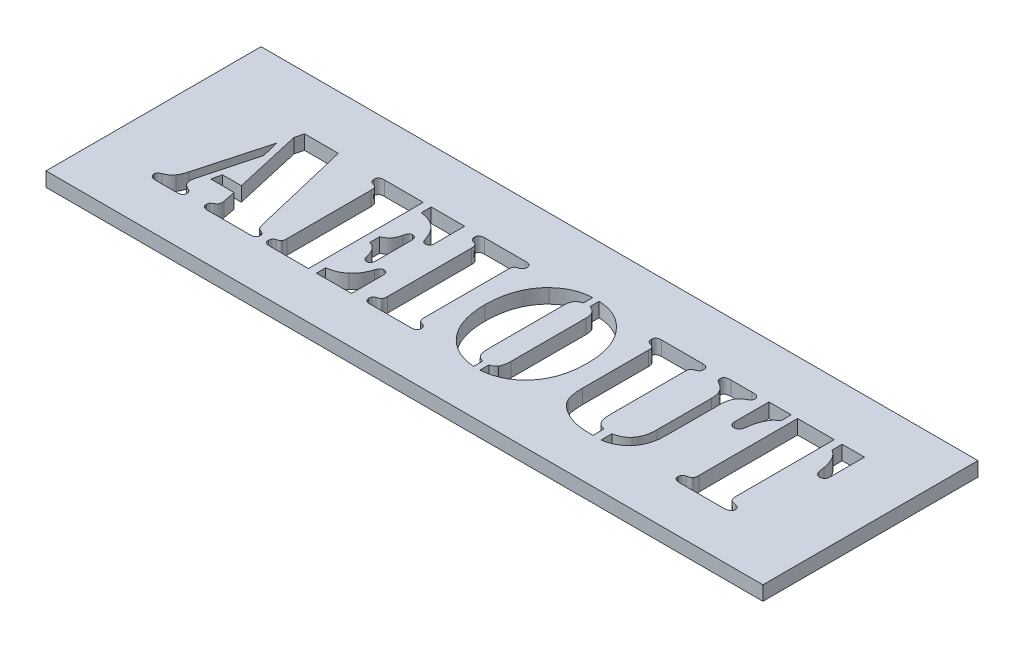
SolidWorks part; units mm, degrees
ref_plane "Front Plane" through (0, 0, 0) normal (0, 0, 1) x (1, 0, 0)
ref_plane "Top Plane" through (0, 0, 0) normal (0, 1, 0) x (1, 0, 0)
ref_plane "Right Plane" through (0, 0, 0) normal (1, 0, 0) x (0, 0, -1)
sketch "Sketch1" plane through (0, 0, 0) normal (0, 1, 0) x (1, 0, 0)
  line L1 (25, 7.5) -> (-25, 7.5)
  line L2 (25, 7.5) -> (25, -7.5)
  line L3 (25, -7.5) -> (-25, -7.5)
  line L4 (-25, 7.5) -> (-25, -7.5)
  line L5 (25, 7.5) -> (-25, -7.5) construction
  line L6 (25, -7.5) -> (-25, 7.5) construction
  point P0 (0, 0)
  dimension "D1" = 50
  dimension "D2" = 15
extrude "Boss-Extrude1" add sketch "Sketch1" along normal blind 1
sketch "Sketch2" plane through (0, 1, 0) normal (0, 1, 0) x (1, 0, 0)
  line L0 (-25, -4.2477) -> (25, -4.2477) construction
  line L1 (-25, 7.5) -> (-25, -7.5) construction
  line L2 (25, -7.5) -> (25, 7.5) construction
  text T0 "AEIOUT" font "Stencil" height 8
extrude "Cut-Extrude1" cut sketch "Sketch2" against normal up to next
